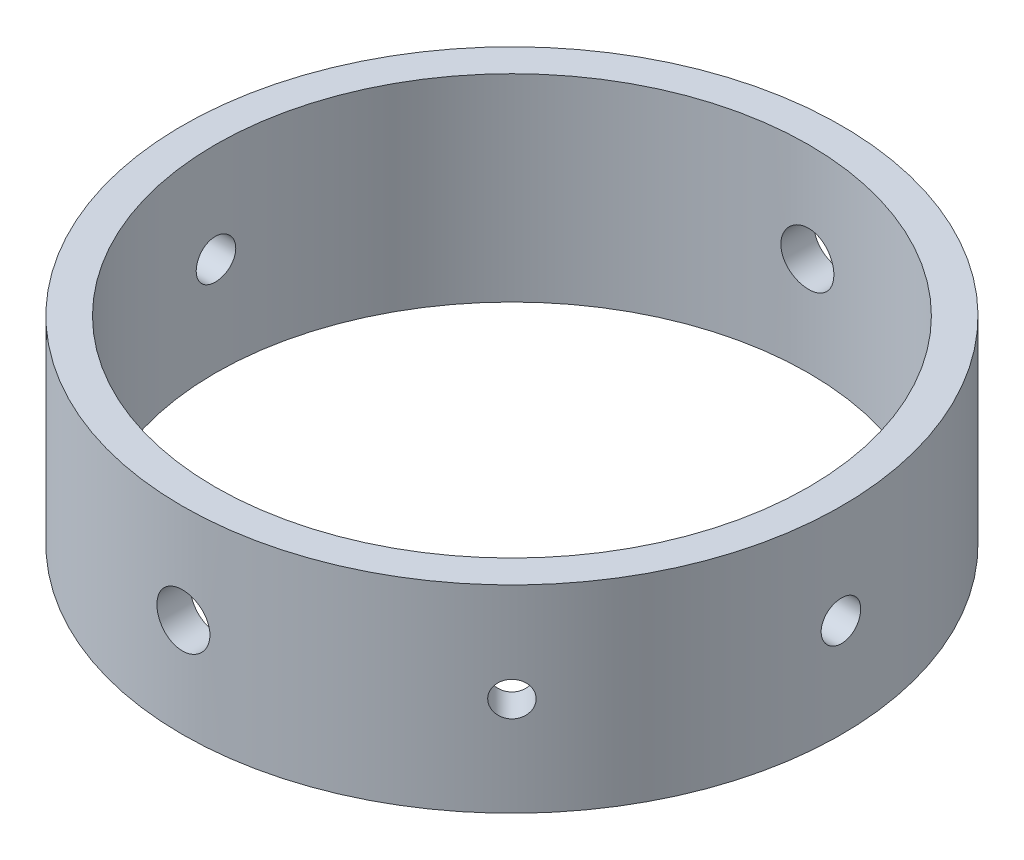
SolidWorks part; units mm, degrees
ref_plane "Front Plane" through (0, 0, 0) normal (0, 0, 1) x (1, 0, 0)
ref_plane "Top Plane" through (0, 0, 0) normal (0, 1, 0) x (1, 0, 0)
ref_plane "Right Plane" through (0, 0, 0) normal (1, 0, 0) x (0, 0, -1)
sketch "Sketch1" plane through (0, 0, 0) normal (0, 1, 0) x (1, 0, 0)
  circle A0 centre (0, 0) radius 31.75
  circle A1 centre (0, 0) radius 28.575
  dimension "D1" = 63.5
  dimension "D2" = 57.15
extrude "Boss-Extrude1" add sketch "Sketch1" along normal blind 19.05
ref_plane "Plane1" through (0, 0, 31.75) normal (0, 0, 1) x (1, 0, 0)
ref_plane "Plane2" through (0, 0, -31.75) normal (0, 0, 1) x (1, 0, 0)
sketch "Sketch3" plane through (0, 0, 31.75) normal (0, 0, 1) x (1, 0, 0)
  line L0 (28.575, 19.05) -> (-28.575, 19.05) construction
  circle A0 centre (0, 9.525) radius 2.7224
  dimension "D1" = 9.525
hole_wizard "Tap Drill for 1/4-20 Tap1" positions "Sketch4" profile "Sketch5" hole size "1/4-20" standard "ANSI Inch" end condition up to next
sketch "Sketch4" plane through (0, 0, 31.75) normal (0, 0, 1) x (1, 0, 0)
  point P0 (0, 9.525)
sketch "Sketch5" plane through (0, 9.525, 31.75) normal (1, 0, 0) x (0, -1, 0)
  line L0 (0, 0) -> (0, 3.175)
  line L1 (0, 3.175) -> (2.5527, 3.175)
  line L2 (2.5527, 3.175) -> (2.5527, 0)
  line L5 (2.5527, 0) -> (0, 0)
  line L11 (0, -6.35) -> (0, 107.95) construction
  dimension "Thru Hole Dia." = 5.1054
  dimension "Thru Hole Depth" = 3.175
sketch "Sketch7" plane through (0, 0, -31.75) normal (0, 0, 1) x (1, 0, 0)
  line L0 (31.75, 19.05) -> (-31.75, 19.05) construction
  circle A0 centre (0, 9.525) radius 3.5632
  dimension "D1" = 9.525
hole_wizard "Tap Drill for 1/4-20 Tap2" positions "Sketch8" profile "Sketch9" hole size "1/4-20" standard "ANSI Inch" end condition up to next
sketch "Sketch8" plane through (0, 0, -31.75) normal (0, 0, 1) x (1, 0, 0)
  point P0 (0, 9.525)
sketch "Sketch9" plane through (0, 9.525, -31.75) normal (1, 0, 0) x (0, 1, 0)
  line L0 (0, 0) -> (0, 3.175)
  line L1 (0, 3.175) -> (2.5527, 3.175)
  line L2 (2.5527, 3.175) -> (2.5527, 0)
  line L5 (2.5527, 0) -> (0, 0)
  line L11 (0, -6.35) -> (0, 107.95) construction
  dimension "Thru Hole Dia." = 5.1054
  dimension "Thru Hole Depth" = 3.175
ref_plane "Plane3" through (31.75, 0, 0) normal (1, 0, 0) x (0, 0, -1)
ref_plane "Plane4" through (-31.75, 0, 0) normal (1, 0, 0) x (0, 0, -1)
sketch "Sketch10" plane through (-31.75, 0, 0) normal (1, 0, 0) x (0, 0, -1)
  circle A0 centre (0, 9.4879) radius 1.905
  dimension "D1" = 3.81
extrude "Cut-Extrude3" cut sketch "Sketch10" against normal through all and the other way through all
sketch3d "3DSketch1"
  point P0 (28.9343, 8.9339, 13.0718)
ref_plane "Plane6" through (21.003, 0, 21.003) normal (0.7071, 0, 0.7071) x (0.7071, 0, -0.7071)
sketch "Sketch12" plane through (21.003, 0, 21.003) normal (0.7071, 0, 0.7071) x (0.7071, 0, -0.7071)
  circle A0 centre (0, 9.525) radius 1.651
extrude "Cut-Extrude4" cut sketch "Sketch12" against normal up to next and the other way through all
